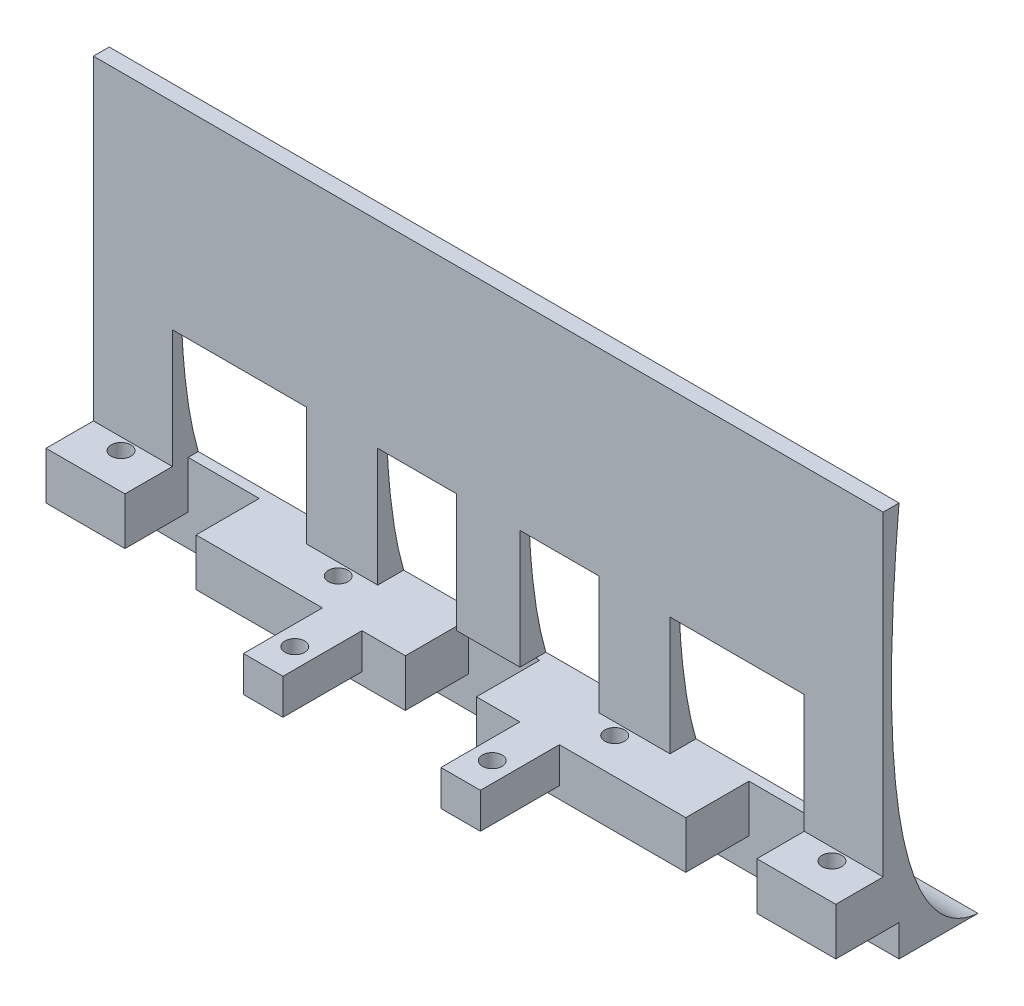
SolidWorks part; units mm, degrees
ref_plane "Płaszczyzna przednia" through (0, 0, 0) normal (0, 0, 1) x (1, 0, 0)
ref_plane "Płaszczyzna górna" through (0, 0, 0) normal (0, 1, 0) x (1, 0, 0)
ref_plane "Płaszczyzna prawa" through (0, 0, 0) normal (1, 0, 0) x (0, 0, -1)
sketch "Szkic1" plane through (0, 0, 0) normal (0, 1, 0) x (1, 0, 0)
  line L0 (0, 0) -> (-100, 0)
  line L1 (-100, 0) -> (-100, 28)
  line L2 (-100, 28) -> (0, 28)
  line L3 (0, 28) -> (0, 0)
  dimension "D1" = 100
  dimension "D2" = 28
extrude "ogolny ksztalt" add sketch "Szkic1" along normal blind 50
sketch "zakrzywuienie" plane through (0, 0, 0) normal (1, 0, 0) x (0, 0, -1)
  line L0 (28, 0) -> (18, 0)
  line L1 (0, 0) -> (28, 0) construction
  line L3 (0, 50) -> (28, 50) construction
  line L4 (18, 0) -> (0, 0)
  line L5 (0, 0) -> (0, 50)
  line L6 (0, 50) -> (18, 50)
  spline S0 degree 3 poles (18, 50) (14.6936, 12.9926) (20.3971, 0.6928) (28, 0) knots 0 0 0 0 1 1 1 1
  dimension "D1" = 10
  dimension "D2" = 18
extrude "wyciecie ksztal przod" cut sketch "zakrzywuienie" against normal blind 105 flip side to cut
sketch "Szkic4" plane through (0, 0, 0) normal (0, -1, 0) x (-1, 0, 0)
  line L0 (65, 0) -> (35, 0)
  line L1 (100, 0) -> (0, 0) construction
  line L2 (100, 28) -> (100, 0) construction
  line L3 (35, 0) -> (35, 10)
  line L4 (65, 0) -> (65, 10)
  line L5 (65, 10) -> (100, 10)
  line L6 (100, 10) -> (100, 0)
  line L7 (100, 0) -> (65, 0)
  line L8 (35, 0) -> (0, 0)
  line L9 (35, 10) -> (0, 10)
  line L10 (0, 0) -> (0, 28) construction
  line L11 (0, 10) -> (0, 0)
  line M4 (0, 28) -> (0, 0)
  line M5 (0, 0) -> (100, 0)
  line M6 (100, 0) -> (100, 28)
  dimension "D1" = 30
  dimension "D2" = 35
  dimension "D3" = 35
  dimension "D4" = 10
  dimension "D5" = 10
extrude "wyciecie ksztaltu tyl" cut sketch "Szkic4" against normal blind 99.5 and the other way blind 23 contours L5 L4 M5 M6 | L3 L9 M4 M5 region at (-17.5, 0, -5) region at (-82.5, 0, -5)
sketch "Szkic5" plane through (0, 0, 0) normal (0, -1, 0) x (-1, 0, 0)
  line L0 (35, 0) -> (65, 0)
  line L1 (65, 0) -> (65, 10)
  line L2 (65, 10) -> (35, 10)
  line L3 (35, 10) -> (35, 0)
extrude "podbicie tyl(spod)" cut sketch "Szkic5" against normal blind 5.5
sketch "Szkic6" plane through (0, 0, 0) normal (0, -1, 0) x (-1, 0, 0)
  line L0 (0, 10) -> (100, 10)
  line L1 (100, 10) -> (100, 18)
  line L2 (100, 28) -> (100, 10) construction
  line L3 (100, 18) -> (0, 18)
  line L4 (0, 10) -> (0, 28) construction
  line L5 (0, 18) -> (0, 10)
  dimension "D1" = 8
extrude "podbicie srodek(spod)" cut sketch "Szkic6" against normal blind 4
sketch "Szkic7" plane through (0, 50, 0) normal (0, 1, 0) x (1, 0, 0)
  line L2 (0, 10) -> (-35, 10)
  line L3 (-35, 10) -> (-35, 0)
  line L4 (-35, 0) -> (-65, 0)
  line L5 (-65, 0) -> (-65, 10)
  line L6 (-65, 10) -> (-100, 10)
  line L8 (-100, 10) -> (-100, 16)
  line L10 (-100, 18) -> (-100, 10) construction
  line L11 (-100, 16) -> (0, 16)
  line L12 (0, 10) -> (0, 18) construction
  line L13 (0, 16) -> (0, 10)
  dimension "D1" = 6
extrude "przyciecie od gory" cut sketch "Szkic7" against normal blind 40
sketch "Szkic8" plane through (0, 5.5, 0) normal (0, -1, 0) x (-1, 0, 0)
  line L0 (0, 28) -> (100, 28) construction
  line L1 (35, 10) -> (35, 0) construction
  line L2 (65, 0) -> (65, 10) construction
  line L3 (100, 10) -> (100, 18) construction
  line L4 (0, 18) -> (0, 10) construction
  circle A0 centre (62.5, 4) radius 1.25
  circle A1 centre (37.5, 4) radius 1.25
  circle A2 centre (67.5, 14.5) radius 1.25
  circle A3 centre (32.5, 14.5) radius 1.25
  circle A4 centre (95, 14.5) radius 1.25
  circle A5 centre (5, 14.5) radius 1.25
  dimension "D6" = 2.5
  dimension "D7" = 2.5
  dimension "D17" = 2.5
  dimension "D18" = 2.5
  dimension "D19" = 2.5
  dimension "D20" = 2.5
  dimension "D1" = 24
  dimension "D2" = 24
  dimension "D3" = 25
  dimension "D4" = 2.5
  dimension "D5" = 2.5
  dimension "D8" = 13.5
  dimension "D9" = 13.5
  dimension "D10" = 35
  dimension "D11" = 13.5
  dimension "D12" = 13.5
  dimension "D13" = 5
  dimension "D14" = 32.5
  dimension "D15" = 5
  dimension "D16" = 32.5
extrude "otwory na sruby" cut sketch "Szkic8" against normal blind 71 and the other way blind 90
sketch "Szkic9" plane through (0, 0, 0) normal (0, -1, 0) x (-1, 0, 0)
  line L0 (0, 28) -> (100, 28) construction
  line L1 (45.5, 18) -> (54.5, 18)
  line L2 (45.5, 18) -> (45.5, 8)
  line L3 (45.5, 8) -> (54.5, 8)
  line L4 (54.5, 18) -> (54.5, 8)
  line L5 (100, 18) -> (0, 18) construction
  line L6 (10, 18) -> (19, 18)
  line L7 (10, 18) -> (10, 8)
  line L8 (10, 8) -> (19, 8)
  line L9 (19, 18) -> (19, 8)
  line L10 (100, 18) -> (0, 18) construction
  line L11 (90, 18) -> (81, 18)
  line L12 (90, 18) -> (90, 8)
  line L13 (90, 8) -> (81, 8)
  line L14 (81, 18) -> (81, 8)
  line L16 (100, 10) -> (100, 18) construction
  dimension "D1" = 10
  dimension "D2" = 9
  dimension "D3" = 10
  dimension "D4" = 26.5
  dimension "D5" = 26.5
  dimension "D6" = 10
  dimension "D7" = 9
  dimension "D8" = 9
  dimension "D9" = 10
  dimension "D10" = 10
  dimension "D11" = 10
extrude "ktir kable" cut sketch "Szkic9" against normal blind 10
sketch "Szkic10" plane through (0, 5.5, 0) normal (0, -1, 0) x (1, 0, 0)
  line L0 (-40, 0) -> (-60, 0)
  line L1 (-35, 0) -> (-65, 0) construction
  line L2 (-60, 0) -> (-60, -10)
  line L3 (0, -10) -> (-10, -10) construction
  line L4 (-60, -10) -> (-40, -10)
  line L5 (-65, -10) -> (-54.5, -10) construction
  line L6 (-40, -10) -> (-40, 0)
  line L7 (-35, -10) -> (-35, 0) construction
  line L8 (-65, 0) -> (-65, -10) construction
  dimension "D1" = 20
  dimension "D2" = 5
  dimension "D3" = 5
extrude "Wytnij-wyciągnięcie3" cut sketch "Szkic10" against normal blind 81 and the other way blind 84
sketch "Szkic11" plane through (0, 0, -16) normal (0, 0, 1) x (1, 0, 0)
  line L0 (-64, 10) -> (-64, 25)
  line L1 (-65, 10) -> (-60, 10) construction
  line L2 (-64, 25) -> (-54, 25)
  line L3 (-54, 25) -> (-54, 10)
  line L4 (-45.5, 10) -> (-54.5, 10) construction
  line L5 (-54, 10) -> (-64, 10)
  line L6 (-65, 5.5) -> (-65, 10) construction
  line L7 (-36, 10) -> (-46, 10)
  line L8 (-40, 10) -> (-35, 10) construction
  line L9 (-40, 10) -> (-45.5, 10) construction
  line L10 (-46, 10) -> (-46, 25)
  line L11 (-46, 25) -> (-36, 25)
  line L12 (-36, 25) -> (-36, 10)
  line L13 (-35, 10) -> (-35, 5.5) construction
  line L14 (-73, 10) -> (-73, 25)
  line L15 (-81, 10) -> (-65, 10) construction
  line L16 (-73, 25) -> (-90, 25)
  line L17 (-90, 25) -> (-90, 10)
  line L18 (-90, 10) -> (-81, 10) construction
  line L19 (-90, 10) -> (-73, 10)
  line L20 (-81, 10) -> (-81, 4) construction
  line L22 (-27, 10) -> (-27, 25)
  line L23 (-35, 10) -> (-19, 10) construction
  line L24 (-27, 25) -> (-10, 25)
  line L25 (-10, 25) -> (-10, 10)
  line L26 (-19, 10) -> (-10, 10) construction
  line L27 (-10, 10) -> (-27, 10)
  line L28 (-19, 4) -> (-19, 10) construction
  dimension "D1" = 1
  dimension "D2" = 10
  dimension "D3" = 15
  dimension "D4" = 1
  dimension "D5" = 10
  dimension "D6" = 15
  dimension "D7" = 17
  dimension "D8" = 8
  dimension "D9" = 8
  dimension "D10" = 15
  dimension "D11" = 17
  dimension "D12" = 15
  dimension "D13" = 8
  dimension "D14" = 8
extrude "Wytnij-wyciągnięcie4" cut sketch "Szkic11" against normal blind 55 and the other way blind 59
